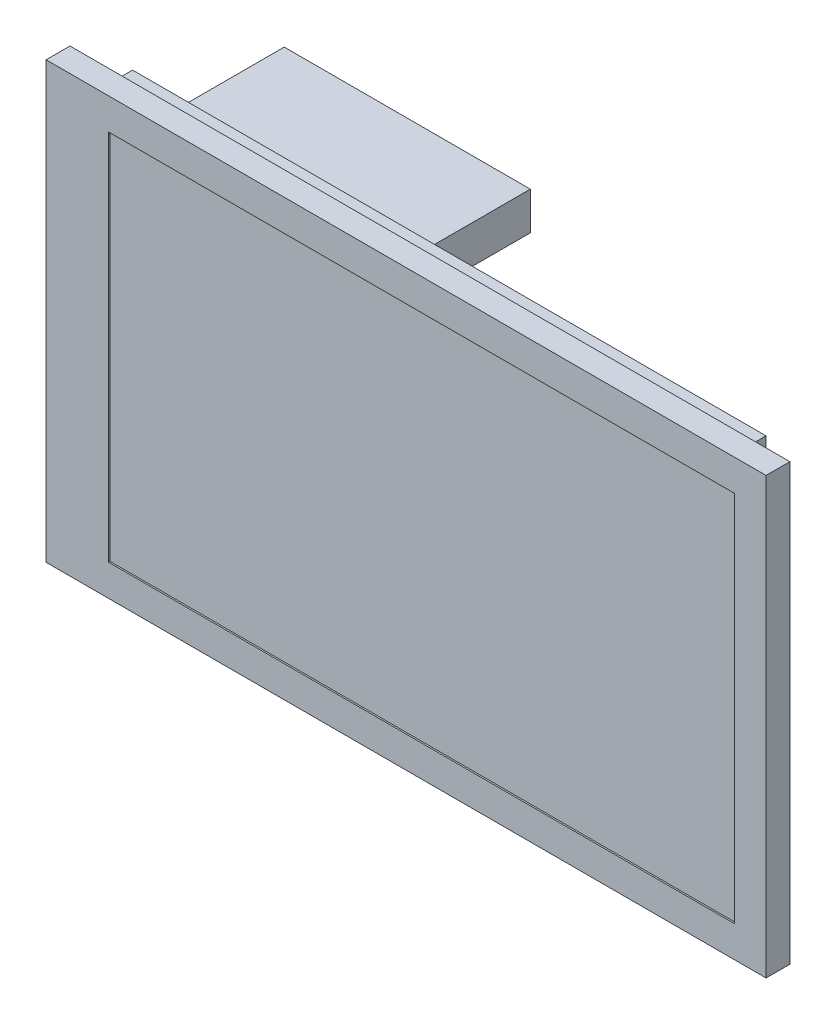
SolidWorks part; units mm, degrees
ref_plane "Front Plane" through (0, 0, 0) normal (0, 0, 1) x (1, 0, 0)
ref_plane "Top Plane" through (0, 0, 0) normal (0, 1, 0) x (1, 0, 0)
ref_plane "Right Plane" through (0, 0, 0) normal (1, 0, 0) x (0, 0, -1)
sketch "Sketch1" plane through (0, 0, 0) normal (0, 0, 1) x (1, 0, 0)
  line L0 (-42, 25) -> (42, -25) construction
  line L1 (-42, 25) -> (42, 25)
  line L2 (-42, 25) -> (-42, -25)
  line L3 (-42, -25) -> (42, -25)
  line L4 (42, 25) -> (42, -25)
  dimension "D1" = 50
  dimension "D2" = 84
extrude "Boss-Extrude1" add sketch "Sketch1" against normal blind 3
sketch "Sketch2" plane through (0, 0, 0) normal (0, 0, 1) x (1, 0, 0)
  line L0 (-50.4, 29.2) -> (-50.4, -29.2)
  line L1 (-42, 25) -> (-42, -25) construction
  line L8 (-46.2, 29.2) -> (-46.2, -29.2)
  line L9 (46.2, 29.2) -> (-46.2, 29.2)
  line L10 (46.2, -29.2) -> (46.2, 29.2)
  line L11 (-46.2, -29.2) -> (46.2, -29.2)
  line L13 (46.2, 29.2) -> (-50.4, 29.2)
  line L14 (46.2, -29.2) -> (46.2, 29.2)
  line L15 (-50.4, -29.2) -> (46.2, -29.2)
  line L18 (-42, 25) -> (-42, -25)
  line L19 (-42, -25) -> (42, -25)
  line L20 (42, -25) -> (42, 25)
  line L21 (42, 25) -> (-42, 25)
  line L22 (-42, 25) -> (-42, -25)
  line L23 (-42, -25) -> (42, -25)
  line L24 (42, -25) -> (42, 25)
  line L25 (42, 25) -> (-42, 25)
  dimension "D2" = 8.4
  dimension "D1" = 4.2
  dimension "D3" = 0
extrude "Boss-Extrude2" add sketch "Sketch2" against normal up to vertex (3 mm away) and the other way blind 0.2 up to point (-42, 25, -3)
sketch "Sketch4" plane through (0, 0, -3) normal (0, 0, -1) x (-1, 0, 0)
  line L8 (44.4, 23.2) -> (-40.2, 23.2)
  line L9 (-40.2, 23.2) -> (-40.2, -23.2)
  line L10 (-40.2, -23.2) -> (44.4, -23.2)
  line L11 (44.4, -23.2) -> (44.4, 23.2)
  line L12 (44.4, 23.2) -> (-40.2, 23.2)
  line L13 (-40.2, 23.2) -> (-40.2, -23.2)
  line L14 (-40.2, -23.2) -> (44.4, -23.2)
  line L15 (44.4, -23.2) -> (44.4, 23.2)
  dimension "D1" = 6
extrude "Boss-Extrude4" add sketch "Sketch4" along normal blind 1
sketch "Sketch5" plane through (0, 0, -4) normal (0, 0, -1) x (-1, 0, 0)
  line L0 (-46.2, 29.2) -> (50.4, -29.2) construction
  line L1 (-40.4, 28) -> (44.6, 28)
  line L2 (-40.4, 28) -> (-40.4, -28)
  line L3 (-40.4, -28) -> (44.6, -28)
  line L4 (44.6, 28) -> (44.6, -28)
  line L6 (-40.4, -28) -> (44.6, 28) construction
  point P8 (2.1, 0)
  dimension "D1" = 56
  dimension "D2" = 85
extrude "Boss-Extrude5" add sketch "Sketch5" along normal blind 1.6
sketch "Sketch6" plane through (0, 0, -5.6) normal (0, 0, -1) x (-1, 0, 0)
  line L0 (35.98, 26.58) -> (37.28, 25.28) construction
  line L1 (35.36, 27.2) -> (37.9, 27.2)
  line L2 (35.36, 27.2) -> (35.36, 24.66)
  line L3 (35.36, 24.66) -> (37.9, 24.66)
  line L4 (37.9, 27.2) -> (37.9, 24.66)
  line L5 (35.98, 26.58) -> (37.28, 26.58)
  line L6 (35.98, 26.58) -> (35.98, 25.28)
  line L7 (35.98, 25.28) -> (37.28, 25.28)
  line L8 (37.28, 26.58) -> (37.28, 25.28)
  line L9 (37.9, 24.66) -> (35.36, 27.2) construction
  line L12 (50.4, 29.2) -> (50.4, -29.2) construction
  line L13 (-46.2, 29.2) -> (50.4, 29.2) construction
  point P8 (36.63, 25.93)
  dimension "D1" = 1.3
  dimension "D2" = 2.54
  dimension "D3" = 12.5
  dimension "D4" = 2
extrude "Boss-Extrude6" add sketch "Sketch6" along normal blind 13.65
pattern_linear "LPattern1" count 13 spacing 2.54 along (1, 0, 0) count 2 spacing 2.54 along (0, -1, 0) of "Boss-Extrude6"
sketch "Sketch7" plane through (0, 0, -5.6) normal (0, 0, -1) x (-1, 0, 0)
  line L0 (44.6, -28) -> (44.6, 28) construction
  line L1 (3, -8) -> (13.2, -8)
  line L2 (3, -8) -> (3, -12.7)
  line L3 (3, -12.7) -> (13.2, -12.7)
  line L4 (13.2, -8) -> (13.2, -12.7)
  line L5 (13.2, -2.9) -> (3, -2.9)
  line L6 (13.2, -2.9) -> (13.2, 1.8)
  line L7 (13.2, 1.8) -> (3, 1.8)
  line L8 (3, -2.9) -> (3, 1.8)
  line L9 (13.2, 10.3) -> (3, 10.3)
  line L10 (13.2, 10.3) -> (13.2, 15)
  line L11 (13.2, 15) -> (3, 15)
  line L12 (3, 10.3) -> (3, 15)
  line L13 (0.8, 15) -> (-9.4, 15)
  line L14 (0.8, 15) -> (0.8, 10.3)
  line L15 (0.8, 10.3) -> (-9.4, 10.3)
  line L16 (-9.4, 15) -> (-9.4, 10.3)
  line L17 (24.3, 3.5) -> (29.6, 3.5)
  line L18 (24.3, 3.5) -> (24.3, -2.1)
  line L19 (24.3, -2.1) -> (29.6, -2.1)
  line L20 (29.6, 3.5) -> (29.6, -2.1)
  line L21 (34.6, 7) -> (38.1, 7)
  line L22 (34.6, 7) -> (34.6, 5.3)
  line L23 (34.6, 5.3) -> (38.1, 5.3)
  line L24 (38.1, 7) -> (38.1, 5.3)
  line L25 (34.6, 4.2) -> (38.3, 4.2)
  line L26 (34.6, 4.2) -> (34.6, -2)
  line L27 (34.6, -2) -> (38.3, -2)
  line L28 (38.3, 4.2) -> (38.3, -2)
  line L29 (34.6, -3.5) -> (38.1, -3.5)
  line L30 (34.6, -3.5) -> (34.6, -5.2)
  line L31 (34.6, -5.2) -> (38.1, -5.2)
  line L32 (38.1, -3.5) -> (38.1, -5.2)
  line L33 (-40.4, -28) -> (44.6, -28) construction
  dimension "D1" = 10.2
  dimension "D2" = 4.7
  dimension "D3" = 5.3
  dimension "D4" = 5.6
  dimension "D5" = 3.7
  dimension "D6" = 6.2
  dimension "D7" = 3.5
  dimension "D8" = 1.7
  dimension "D9" = 10
  dimension "D10" = 20.3
  dimension "D11" = 41.6
  dimension "D12" = 54
  dimension "D13" = 20
  dimension "D14" = 29.8
  dimension "D15" = 43
  dimension "D16" = 31.5
  dimension "D17" = 24.5
  dimension "D18" = 32.2
  dimension "D19" = 35
extrude "Boss-Extrude7" add sketch "Sketch7" along normal blind 1.7
sketch "Sketch8" plane through (0, 0, -5.6) normal (0, 0, -1) x (-1, 0, 0)
  line L0 (-32.7, 22.5339) -> (-32.7, -24.5934) construction
  line L1 (-40.4, 28) -> (-40.4, -28) construction
  text T0 "3.5inch RPi LCD (A)" font "Arial Narrow" height 3.7
  dimension "D1" = 7.7
extrude "Boss-Extrude8" add sketch "Sketch8" along normal blind 0.1
